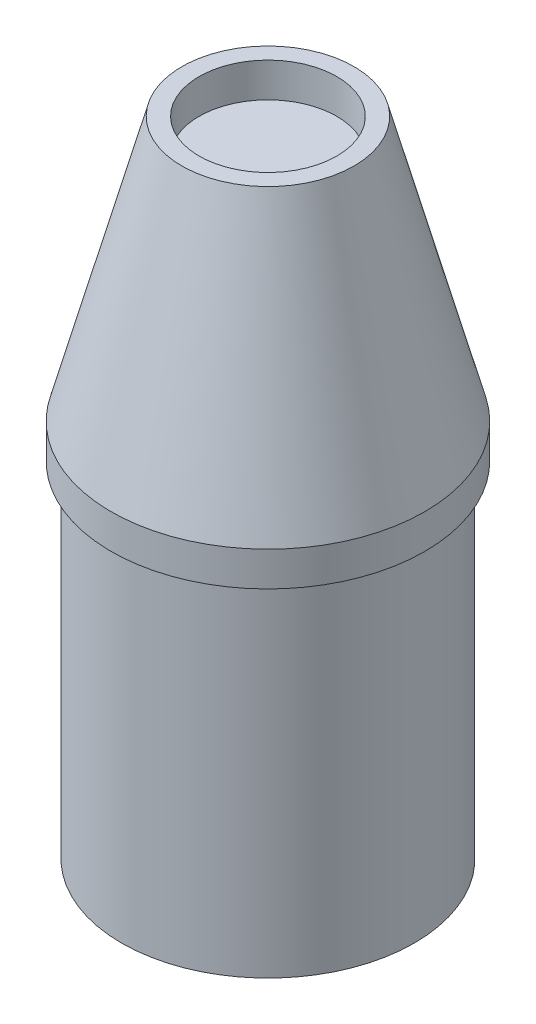
SolidWorks part; units mm, degrees
material "6061 Alloy"
ref_plane "Front Plane" through (0, 0, 0) normal (0, 0, 1) x (1, 0, 0)
ref_plane "Top Plane" through (0, 0, 0) normal (0, 1, 0) x (1, 0, 0)
ref_plane "Right Plane" through (0, 0, 0) normal (1, 0, 0) x (0, 0, -1)
sketch "Sketch1" plane through (0, 0, 0) normal (0, 0, 1) x (1, 0, 0)
  line L0 (0, 6.35) -> (0, 118.5268)
  line L1 (0, 118.5268) -> (12.7, 118.5268)
  line L2 (12.7, 118.5268) -> (12.7, 124.8768)
  line L3 (12.7, 124.8768) -> (15.875, 124.8768)
  line L4 (15.875, 124.8768) -> (28.9179, 76.2)
  line L5 (28.9179, 76.2) -> (28.9179, 69.85)
  line L6 (28.9179, 69.85) -> (26.9875, 69.85)
  line L7 (26.9875, 69.85) -> (26.9875, 6.35)
  line L8 (26.9875, 6.35) -> (0, 6.35)
  point P10 (11.4329, 78.234)
  point P11 (28.9179, 63.5)
  point P12 (0, 0)
  point P13 (28.9179, 69.85)
  point P15 (0, 0)
  point P16 (28.9179, 76.2)
  dimension "D1" = 28.9179
  dimension "D2" = 15
  dimension "D3" = 15.875
  dimension "D5" = 63.5
  dimension "D6" = 6.35
  dimension "D7" = 12.7
  dimension "D8" = 26.9875
revolve "Revolve1" add sketch "Sketch1" angle 360 about L0
